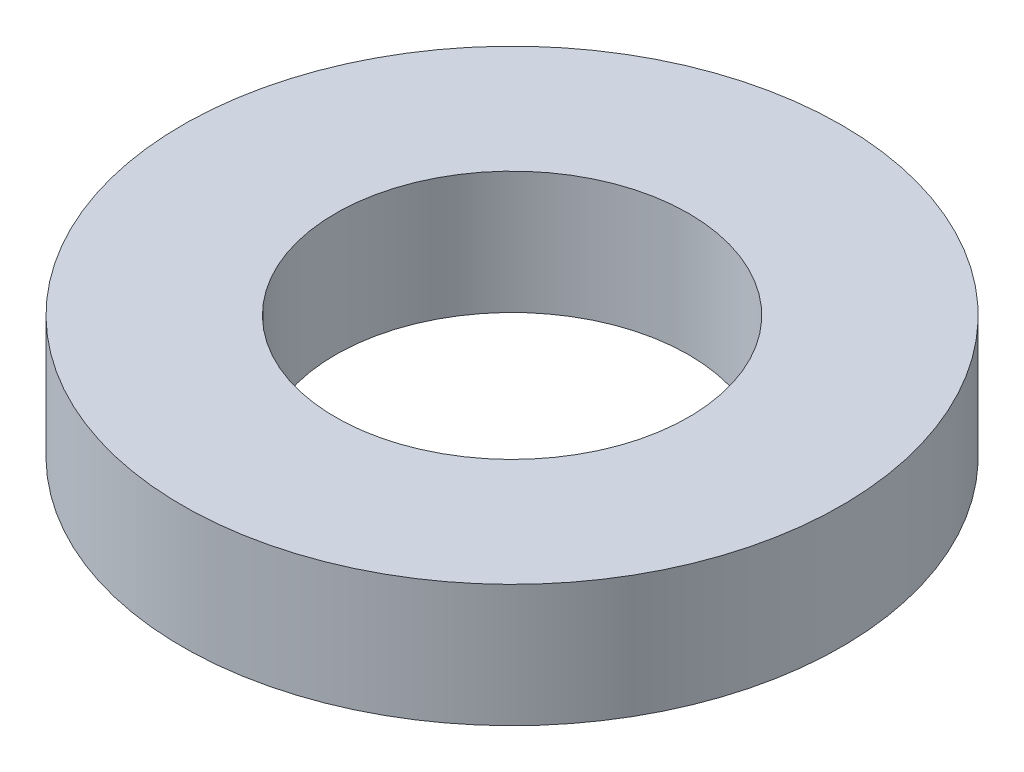
SolidWorks part; units mm, degrees
ref_plane "Front Plane" through (0, 0, 0) normal (0, 0, 1) x (1, 0, 0)
ref_plane "Top Plane" through (0, 0, 0) normal (0, 1, 0) x (1, 0, 0)
ref_plane "Right Plane" through (0, 0, 0) normal (1, 0, 0) x (0, 0, -1)
sketch "Sketch1" plane through (0, 0, 0) normal (0, 1, 0) x (1, 0, 0)
  circle A0 centre (0, 0) radius 70
  dimension "FLANGE_OD" = 140
extrude "Boss-Extrude1" add sketch "Sketch1" along normal blind 26
sketch "Sketch2" plane through (0, 0, 0) normal (0, 1, 0) x (1, 0, 0)
  circle A0 centre (0, 0) radius 37.5
  dimension "BORE_D" = 75
extrude "Cut-Extrude1" cut sketch "Sketch2" along normal through all
sketch "Sketch3" plane through (0, 26, 0) normal (0, 1, 0) x (1, 0, 0)
  circle A0 centre (0, 0) radius 32.4068 construction
  circle A1 centre (-32.4068, 0) radius 1.8476
  dimension "BOLT_D" = 3.6952
  dimension "BOLT_PCD" = 64.8135
extrude "Cut-Extrude2" cut sketch "Sketch3" against normal blind 17.3186 rebuild error yes
pattern_circular "CirPattern1" count 5 over 360 rebuild error yes
